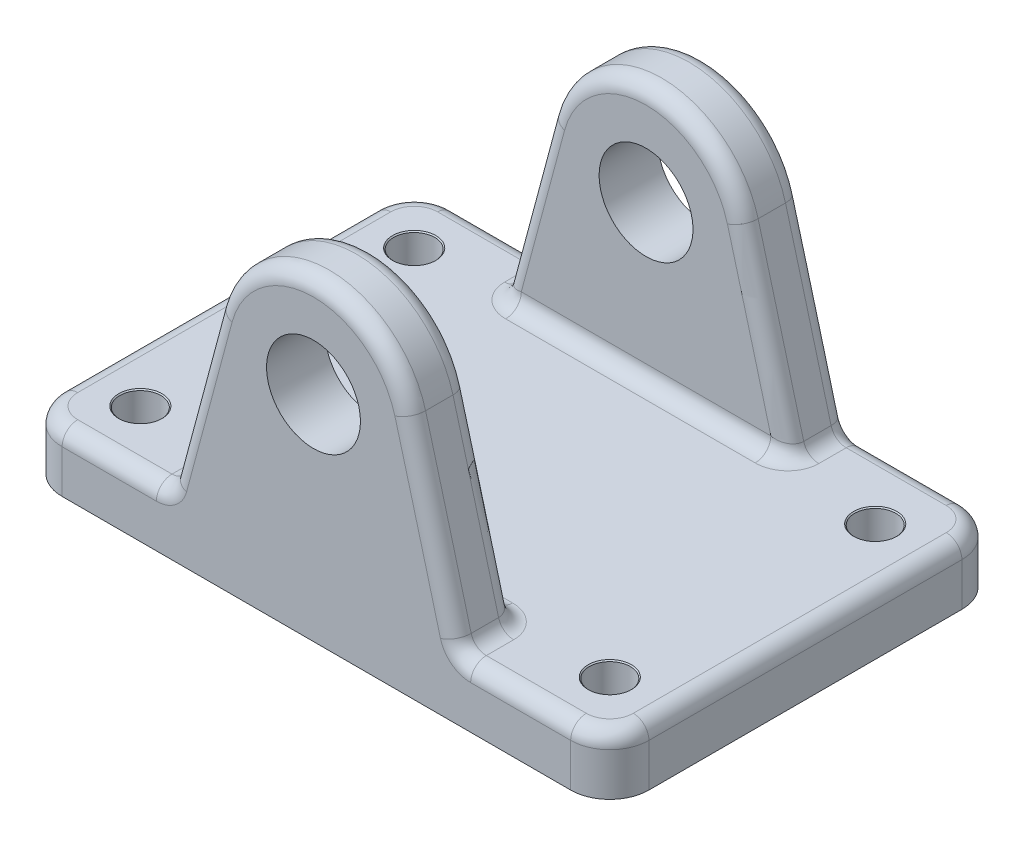
SolidWorks part; units mm, degrees
ref_plane "Front Plane" through (0, 0, 0) normal (0, 0, 1) x (1, 0, 0)
ref_plane "Top Plane" through (0, 0, 0) normal (0, 1, 0) x (1, 0, 0)
ref_plane "Right Plane" through (0, 0, 0) normal (1, 0, 0) x (0, 0, -1)
sketch "Sketch2" plane through (0, 0, 0) normal (0, 1, 0) x (1, 0, 0)
  line L1 (-75, 50) -> (75, 50)
  line L2 (-75, 50) -> (-75, -50)
  line L3 (-75, -50) -> (75, -50)
  line L4 (75, 50) -> (75, -50)
  line L5 (-75, 50) -> (75, -50) construction
  line L6 (-75, -50) -> (75, 50) construction
  point P0 (0, 0)
  dimension "D1" = 150
  dimension "D2" = 100
extrude "Boss-Extrude1" add sketch "Sketch2" along normal blind 15
sketch "Sketch3" plane through (0, 0, 50) normal (0, 0, 1) x (1, 0, 0)
  line L0 (-37.8323, 15) -> (-25.4141, 61.3453)
  line L1 (-75, 15) -> (75, 15) construction
  line L2 (36.3547, 15) -> (-37.8323, 15)
  line L3 (-0.7388, 54.7336) -> (-0.7388, 0) construction
  line L4 (-75, 0) -> (75, 0) construction
  arc A0 (-25.4141, 61.3453) -> (23.9136, 61.4304) centre (-0.7388, 54.7336) cw
  arc A1 (23.9136, 61.4304) -> (36.3547, 15) centre (-6705.3211, -1766.5674) cw
  point P8 (0, 0)
  point P9 (-83.9131, 52.559)
  point P10 (-82.5499, 28.4105)
  point P11 (0, 0)
  point P12 (0, 0)
  point P13 (25.1449, 71.0666)
  point P14 (0, 0)
  point P15 (0, 0)
  point P16 (-21.7424, 66.6072)
  point P17 (25.1237, 66.7566)
  point P18 (0, 0)
  point P19 (0, 0)
  point P20 (0, 0)
  point P21 (0, 0)
  point P22 (0, 0)
  point P23 (0, 0)
  point P24 (0, 0)
  point P28 (0, 0)
  point P29 (0, 0)
  point P30 (36.3547, 15)
  point P31 (36.3547, 15)
  dimension "D3" = 75
extrude "Boss-Extrude2" add sketch "Sketch3" against normal blind 15
sketch "Sketch4" plane through (0, 0, 50) normal (0, 0, 1) x (1, 0, 0)
  circle A0 centre (-0.7388, 54.7336) radius 12
  point P2 (0, 0)
  point P3 (-0.7388, 54.7336)
  point P5 (0, 54.7336)
  point P6 (0, 0)
  point P7 (0, 54.7336)
extrude "Cut-Extrude1" cut sketch "Sketch4" against normal through all
mirror "Mirror1" about plane through (0, 0, 0) normal (0, 0, 1) of "Boss-Extrude2", "Cut-Extrude1"
hole_wizard "M10 Clearance Hole1" positions "Sketch5" profile "Sketch6" hole size "M10" standard "ANSI Metric" end condition through all
sketch "Sketch5" plane through (0, 15, 0) normal (0, 1, 0) x (1, 0, 0)
  line L0 (-75, 50) -> (-75, -50) construction
  line L1 (75, -50) -> (75, 50) construction
  line L4 (36.3547, -50) -> (75, -50) construction
  line L5 (-37.8323, 50) -> (-75, 50) construction
  point P0 (-60, 35)
  point P2 (-60, -35)
  point P4 (60, -35)
  point P6 (60, 32.8464)
  dimension "D1" = 15
  dimension "D2" = 15
  dimension "D3" = 15
  dimension "D4" = 15
  dimension "D5" = 67.8464
sketch "Sketch6" plane through (-60, 15, -35) normal (1, 0, 0) x (0, 0, 1)
  line L0 (0, 0) -> (0, 15)
  line L1 (0, 15) -> (5.25, 15)
  line L2 (5.25, 15) -> (5.25, 0.275)
  line L3 (5.25, 0.275) -> (5.525, 0)
  line L5 (5.525, 0) -> (0, 0)
  line L6 (-5.25, 0.275) -> (-5.525, 0) construction
  line L11 (0, -6.35) -> (0, 107.95) construction
  dimension "Thru Hole Dia." = 10.5
  dimension "Thru Hole Depth" = 15
  dimension "Near C'Sink Dia." = 11.05
  dimension "Near C'Sink Angle" = 90
fillet "Fillet1" radius 10 4 edges at (75, 7.5, 50) (75, 7.5, -50) (-75, 7.5, 50) (-75, 7.5, -50)
fillet "Fillet2" radius 4 28 edges at (-0.7388, 15, 35) (-0.7388, 15, -35) (30.1742, 38.2259, 35) (-31.6232, 38.1727, 35) (30.1742, 38.2259, -35) (30.1742, 38.2259, 50) (-31.6232, 38.1727, 50) (50.6774, 15, 50) (72.0711, 15, 47.0711) (75, 15, 0) (72.0711, 15, -47.0711) (30.1742, 38.2259, -50) (-0.7828, 80.2793, -50) (-51.4161, 15, 50) (-72.0711, 15, 47.0711) (-75, 15, 0) (-72.0711, 15, -47.0711) (36.3547, 15, -42.5) (36.3547, 15, 42.5) (-37.8323, 15, 42.5) (-0.7828, 80.2793, 35) (-31.6232, 38.1727, -35) (-0.7828, 80.2793, -35) (-37.8323, 15, -42.5) (-0.7828, 80.2793, 50) (50.6774, 15, -50) (-31.6232, 38.1727, -50) (-51.4161, 15, -50)
